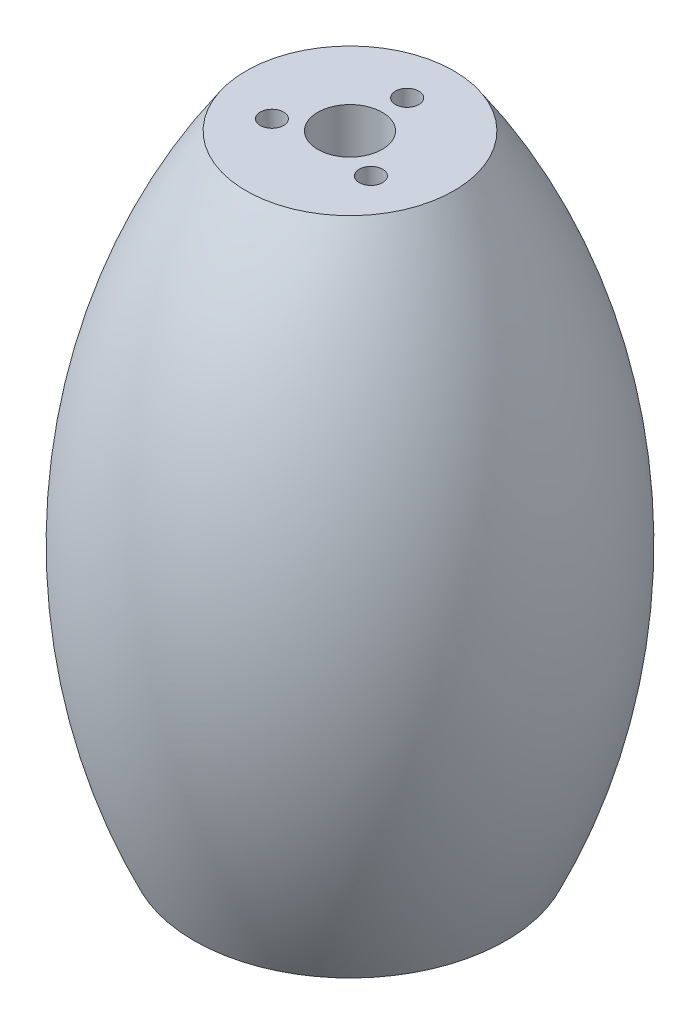
SolidWorks part; units mm, degrees
ref_plane "正面" through (0, 0, 0) normal (0, 0, 1) x (1, 0, 0)
ref_plane "平面" through (0, 0, 0) normal (0, 1, 0) x (1, 0, 0)
ref_plane "右側面" through (0, 0, 0) normal (1, 0, 0) x (0, 0, -1)
sketch "ｽｹｯﾁ1" plane through (0, 0, 0) normal (0, 0, 1) x (1, 0, 0)
  line L0 (-30, 0) -> (0, 0)
  line L1 (0, 0) -> (0, 120)
  line L2 (0, 120) -> (-20, 120)
  arc A0 (-30, 0) -> (-20, 120) centre (80, 51.25) cw
  dimension "D1" = 120
  dimension "D2" = 30
  dimension "D3" = 20
  dimension "D4" = 80
revolve "回転1" add sketch "ｽｹｯﾁ1" angle 360 about L1
sketch "ｽｹｯﾁ2" plane through (0, 120, 0) normal (0, 1, 0) x (1, 0, 0)
  line L0 (0, 0) -> (0, 11) construction
  line L1 (-9.5263, -5.5) -> (0, 0) construction
  line L2 (0, 0) -> (9.5263, -5.5) construction
  circle A0 centre (0, 11) radius 2.25
  circle A1 centre (9.5263, -5.5) radius 2.25
  circle A2 centre (-9.5263, -5.5) radius 2.25
  dimension "D1" = 4.5
  dimension "D2" = 11
  dimension "D3" = 3
extrude "ｶｯﾄ - 押し出し1" cut sketch "ｽｹｯﾁ2" against normal blind 5
ref_plane "平面1" through (0, 60, 0) normal (0, 1, 0) x (1, 0, 0)
mirror "ﾐﾗｰ1" about plane through (0, 60, 0) normal (0, 1, 0) of "ｶｯﾄ - 押し出し1"
sketch "ｽｹｯﾁ3" plane through (0, 120, 0) normal (0, 1, 0) x (1, 0, 0)
  circle A0 centre (0, 0) radius 6.2
  dimension "D1" = 12.4
extrude "ｶｯﾄ - 押し出し2" cut sketch "ｽｹｯﾁ3" against normal through all
